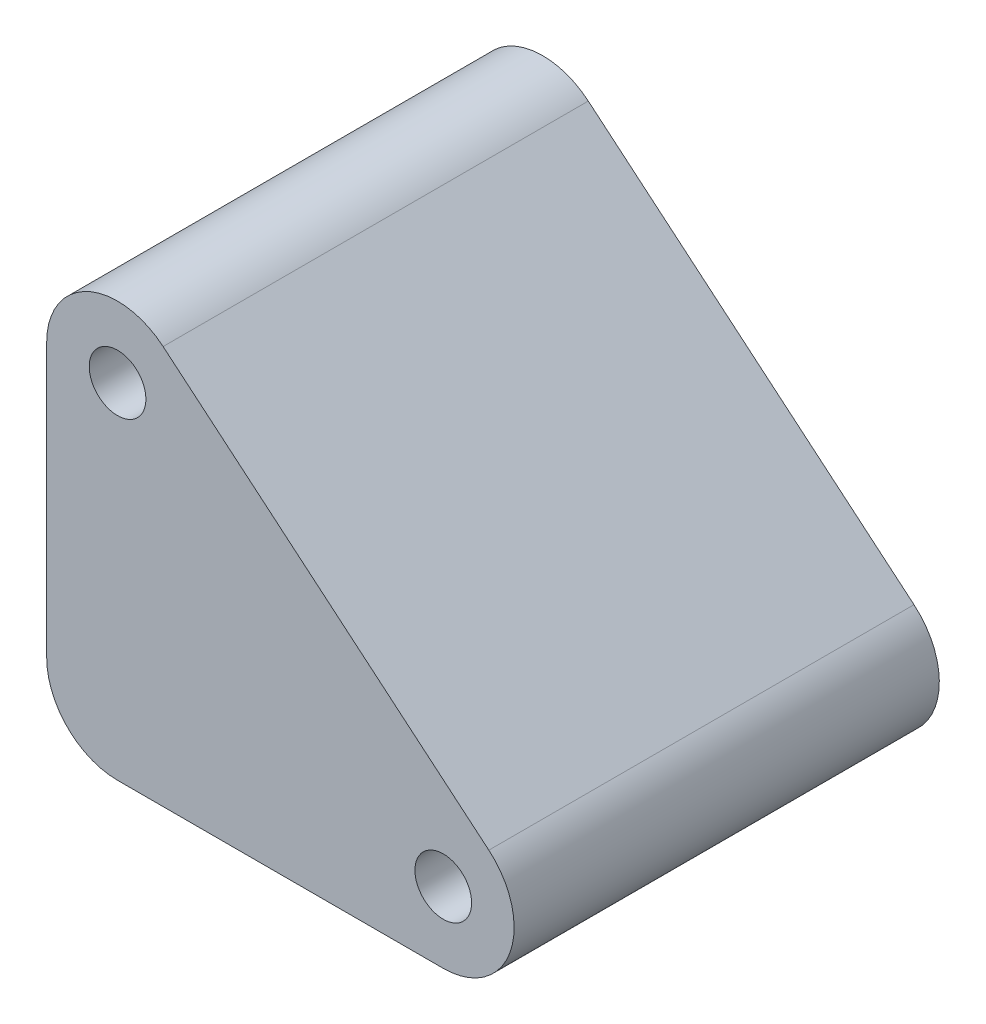
SolidWorks part; units mm, degrees
ref_plane "Front Plane" through (0, 0, 0) normal (0, 0, 1) x (1, 0, 0)
ref_plane "Top Plane" through (0, 0, 0) normal (0, 1, 0) x (1, 0, 0)
ref_plane "Right Plane" through (0, 0, 0) normal (1, 0, 0) x (0, 0, -1)
sketch "Sketch1" plane through (0, 0, 0) normal (0, 0, 1) x (1, 0, 0)
  line L0 (-256.5743, 135.3883) -> (-233.593, 116.1047)
  line L1 (-236.8069, 107.2745) -> (-259.7883, 107.2745)
  line L2 (-264.7883, 112.2745) -> (-264.7883, 131.5581)
  circle A0 centre (-236.8069, 112.2745) radius 2 construction
  circle A1 centre (-259.7883, 131.5581) radius 2 construction
  circle A2 centre (-236.8069, 112.2745) radius 2
  circle A3 centre (-259.7883, 131.5581) radius 2
  arc A4 (-233.593, 116.1047) -> (-236.8069, 107.2745) centre (-236.8069, 112.2745) cw
  arc A5 (-259.7883, 107.2745) -> (-264.7883, 112.2745) centre (-259.7883, 112.2745) cw
  arc A6 (-264.7883, 131.5581) -> (-256.5743, 135.3883) centre (-259.7883, 131.5581) cw
  dimension "D1" = 5
  dimension "D2" = 5
  dimension "D3" = 5
  dimension "D4" = 19.2836
  dimension "D5" = 22.9813
extrude "Boss-Extrude1" add sketch "Sketch1" along normal blind 15 and the other way blind 15
